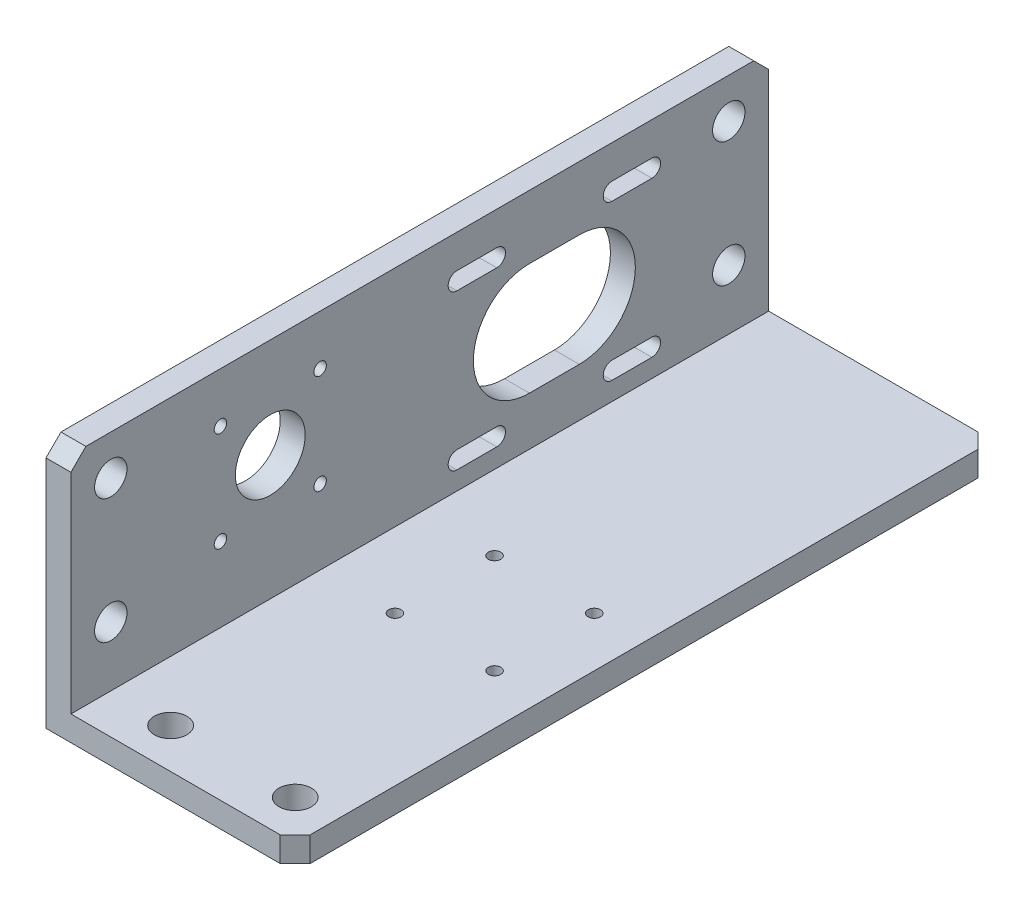
SolidWorks part; units mm, degrees
material "Lega 1060"
ref_plane "Piano frontale" through (0, 0, 0) normal (0, 0, 1) x (1, 0, 0)
ref_plane "Piano superiore" through (0, 0, 0) normal (0, 1, 0) x (1, 0, 0)
ref_plane "Piano destro" through (0, 0, 0) normal (1, 0, 0) x (0, 0, -1)
sketch "Schizzo1" plane through (0, 0, 0) normal (0, 0, 1) x (1, 0, 0)
  line L0 (0, 0) -> (0, 50)
  line L1 (0, 50) -> (5, 50)
  line L2 (5, 50) -> (5, 5)
  line L3 (5, 5) -> (50, 5)
  line L4 (50, 5) -> (50, 0)
  line L5 (50, 0) -> (0, 0)
  dimension "D1" = 5
  dimension "D2" = 5
  dimension "D3" = 50
  dimension "D4" = 50
extrude "Estrusione-Estrusione1" add sketch "Schizzo1" along normal blind 140
sketch "Schizzo2" plane through (0, 0, 0) normal (0, -1, 0) x (1, 0, 0)
  line L0 (5.4524, 132) -> (42.7933, 132) construction
  line L1 (0, 140) -> (50, 140) construction
  line L5 (50, 140) -> (50, 0) construction
  point P4 (17, 132)
  point P5 (42, 132)
  dimension "D1" = 8
  dimension "D2" = 25
  dimension "D3" = 8
sketch "Schizzo3" plane through (0, 0, 0) normal (-1, 0, 0) x (0, 0, 1)
  line L0 (132, 44.621) -> (132, 5.772) construction
  line L1 (140, 50) -> (140, 0) construction
  line L2 (140, 50) -> (0, 50) construction
  point P4 (132, 42)
  point P5 (132, 17)
  dimension "D1" = 8
  dimension "D2" = 8
  dimension "D3" = 25
hole_wizard "Foro Ø6.5 (6.5)-1" positions "Schizzo5" profile "Schizzo4" hole size "Ø6.5" standard "ISO" end condition through all
sketch "Schizzo5" plane through (0, 0, 0) normal (0, -1, 0) x (-1, 0, 0)
  point P0 (-17, -132)
  point P3 (-42, -132)
sketch "Schizzo4" plane through (17, 0, 132) normal (1, 0, 0) x (0, 0, -1)
  line L0 (0, 0) -> (0, 50)
  line L1 (0, 50) -> (3.25, 50)
  line L2 (3.25, 50) -> (3.25, 0)
  line L5 (3.25, 0) -> (0, 0)
  line L11 (0, -6.35) -> (0, 107.95) construction
  dimension "Thru Hole Dia." = 6.5
  dimension "Thru Hole Depth" = 50
hole_wizard "Foro Ø6.5 (6.5)-2" positions "Schizzo7" profile "Schizzo6" hole size "Ø6.5" standard "ISO"
sketch "Schizzo7" plane through (0, 0, 0) normal (-1, 0, 0) x (0, 0, 1)
  point P1 (132, 42)
  point P4 (132, 17)
sketch "Schizzo6" plane through (0, 42, 132) normal (0, 1, 0) x (0, 0, 1)
  line L0 (0, 0) -> (0, 6.9528)
  line L1 (0, 6.9528) -> (3.25, 5)
  line L2 (3.25, 5) -> (3.25, 0)
  line L5 (3.25, 0) -> (0, 0)
  line L10 (0, 6.9528) -> (-3.25, 5) construction
  line L11 (0, -6.35) -> (0, 107.95) construction
  dimension "Hole Dia." = 6.5
  dimension "Hole Depth" = 5
  dimension "Drill Angle" = 118
ref_plane "Piano1" through (0, 0, 70) normal (0, 0, 1) x (1, 0, 0)
mirror "Specchia1" about plane through (0, 0, 70) normal (0, 0, 1) of "Foro Ø6.5 (6.5)-2"
sketch "Schizzo8" plane through (0, 0, 0) normal (0, -1, 0) x (1, 0, 0)
  line L0 (30, 80) -> (7.0316, 80) construction
  line L1 (30, 80) -> (-7.1051, 42.8949) construction
  line L2 (0, 140) -> (50, 140) construction
  line L3 (50, 140) -> (50, 0) construction
  circle A0 centre (20, 70) radius 1.75
  circle A1 centre (20, 90) radius 1.75
  circle A2 centre (40, 90) radius 1.75
  circle A3 centre (40, 70) radius 1.75
  point P18 (30, 80)
  dimension "D3" = 3.5
  dimension "D1" = 60
  dimension "D2" = 20
  dimension "D4" = 45
  dimension "D5" = 20
  dimension "D6" = 4
sketch "Schizzo9" plane through (0, 0, 0) normal (-1, 0, 0) x (0, 0, 1)
  line L2 (140, 50) -> (0, 50) construction
  line L3 (140, 50) -> (140, 0) construction
  circle A4 centre (100, 30) radius 7
  point P18 (100, 30)
  dimension "D7" = 14
  dimension "D1" = 20
  dimension "D2" = 40
extrude "Taglio-Estrusione2" cut sketch "Schizzo9" against normal up to next
sketch "Schizzo11" plane through (0, 0, 0) normal (-1, 0, 0) x (0, 0, 1)
  line L0 (32.6037, 26) -> (56.4009, 26) construction
  line L1 (62.5563, 10.4437) -> (54.5563, 10.4437) construction
  line L2 (140, 0) -> (0, 0) construction
  line L3 (62.5563, 41.5563) -> (54.5563, 41.5563) construction
  line L4 (62.5563, 39.8063) -> (54.5563, 39.8063)
  line L5 (62.5563, 43.3063) -> (54.5563, 43.3063)
  line L6 (43, 26) -> (43, 48.418) construction
  line L7 (62.5563, 12.1937) -> (54.5563, 12.1937)
  line L8 (62.5563, 8.6937) -> (54.5563, 8.6937)
  line L9 (23.4437, 10.4437) -> (31.4437, 10.4437) construction
  line L10 (23.4437, 12.1937) -> (31.4437, 12.1937)
  line L11 (23.4437, 8.6937) -> (31.4437, 8.6937)
  line L12 (23.4437, 41.5563) -> (31.4437, 41.5563) construction
  line L13 (23.4437, 39.8063) -> (31.4437, 39.8063)
  line L14 (23.4437, 43.3063) -> (31.4437, 43.3063)
  line L15 (48, 26) -> (38, 26) construction
  line L16 (48, 14.75) -> (38, 14.75)
  line L17 (48, 37.25) -> (38, 37.25)
  arc A1 (62.5563, 39.8063) -> (62.5563, 43.3063) centre (62.5563, 41.5563) ccw
  arc A2 (62.5563, 12.1937) -> (62.5563, 8.6937) centre (62.5563, 10.4437) cw
  arc A3 (54.5563, 8.6937) -> (54.5563, 12.1937) centre (54.5563, 10.4437) cw
  arc A4 (23.4437, 12.1937) -> (23.4437, 8.6937) centre (23.4437, 10.4437) ccw
  arc A5 (31.4437, 8.6937) -> (31.4437, 12.1937) centre (31.4437, 10.4437) ccw
  arc A7 (54.5563, 43.3063) -> (54.5563, 39.8063) centre (54.5563, 41.5563) ccw
  arc A8 (23.4437, 39.8063) -> (23.4437, 43.3063) centre (23.4437, 41.5563) cw
  arc A9 (31.4437, 43.3063) -> (31.4437, 39.8063) centre (31.4437, 41.5563) cw
  arc A10 (48, 14.75) -> (48, 37.25) centre (48, 26) ccw
  arc A11 (38, 37.25) -> (38, 14.75) centre (38, 26) ccw
  point P10 (58.5563, 10.4437)
  point P13 (58.5563, 41.5563)
  point P18 (27.4437, 10.4437)
  point P20 (43, 26)
  point P33 (27.4437, 41.5563)
  point P40 (43, 26)
  dimension "D5" = 10
  dimension "D1" = 22.5
  dimension "D4" = 26
  dimension "D8" = 3.5
  dimension "D9" = 8
extrude "Taglio-Estrusione4" cut sketch "Schizzo11" against normal up to next
chamfer "Smusso1" distance 3 angle 45 4 edges at (50, 2.5, 0) (2.5, 50, 0) (2.5, 50, 140) (50, 2.5, 140)
sketch "Sketch4" plane through (0, 0, 0) normal (-1, 0, 0) x (0, 0, 1)
  line L0 (100, 30) -> (100, 45.3374) construction
  line L1 (100, 30) -> (85.4455, 44.5545) construction
  line L2 (100, 30) -> (85.4455, 30) construction
  point P3 (90, 40)
  point P5 (110, 40)
  point P6 (90, 20)
  point P8 (110, 20)
  dimension "D1" = 45
  dimension "D2" = 10
hole_wizard "M3 Tapped Hole1" positions "3DSketch3" profile "Sketch5" tap size "M3" standard "ISO" end condition through all
sketch3d "3DSketch3"
  point P0 (0, 40, 90)
  point P3 (0, 40, 110)
  point P6 (0, 20, 110)
  point P9 (0, 20, 90)
sketch "Sketch5" plane through (0, 40, 90) normal (0, 1, 0) x (0, 0, 1)
  line L0 (0, 0) -> (0, 50)
  line L1 (0, 50) -> (1.25, 50)
  line L2 (1.25, 50) -> (1.25, 0)
  line L5 (1.25, 0) -> (0, 0)
  line L11 (0, -6.35) -> (0, 107.95) construction
  dimension "Thru Tap Drill Dia." = 2.5
  dimension "Thru Tap Drill Depth" = 50
cosmetic thread "Cosmetic Thread1" parameters "D2"=3
cosmetic thread "Cosmetic Thread2" parameters "D2"=3
cosmetic thread "Cosmetic Thread3" parameters "D2"=3
cosmetic thread "Cosmetic Thread4" parameters "D2"=3
hole_wizard "M3 Tapped Hole2" positions "3DSketch4" profile "Sketch6" tap size "M3" standard "ISO" end condition through all
sketch3d "3DSketch4"
  point P0 (20, 0, 90)
  point P3 (40, 0, 90)
  point P6 (40, 0, 70)
  point P9 (20, 0, 70)
sketch "Sketch6" plane through (20, 0, 90) normal (1, 0, 0) x (0, 0, -1)
  line L0 (0, 0) -> (0, 50)
  line L1 (0, 50) -> (1.25, 50)
  line L2 (1.25, 50) -> (1.25, 0)
  line L5 (1.25, 0) -> (0, 0)
  line L11 (0, -6.35) -> (0, 107.95) construction
  dimension "Thru Tap Drill Dia." = 2.5
  dimension "Thru Tap Drill Depth" = 50
cosmetic thread "Cosmetic Thread5" parameters "D2"=3
cosmetic thread "Cosmetic Thread6" parameters "D2"=3
cosmetic thread "Cosmetic Thread7" parameters "D2"=3
cosmetic thread "Cosmetic Thread8" parameters "D2"=3
